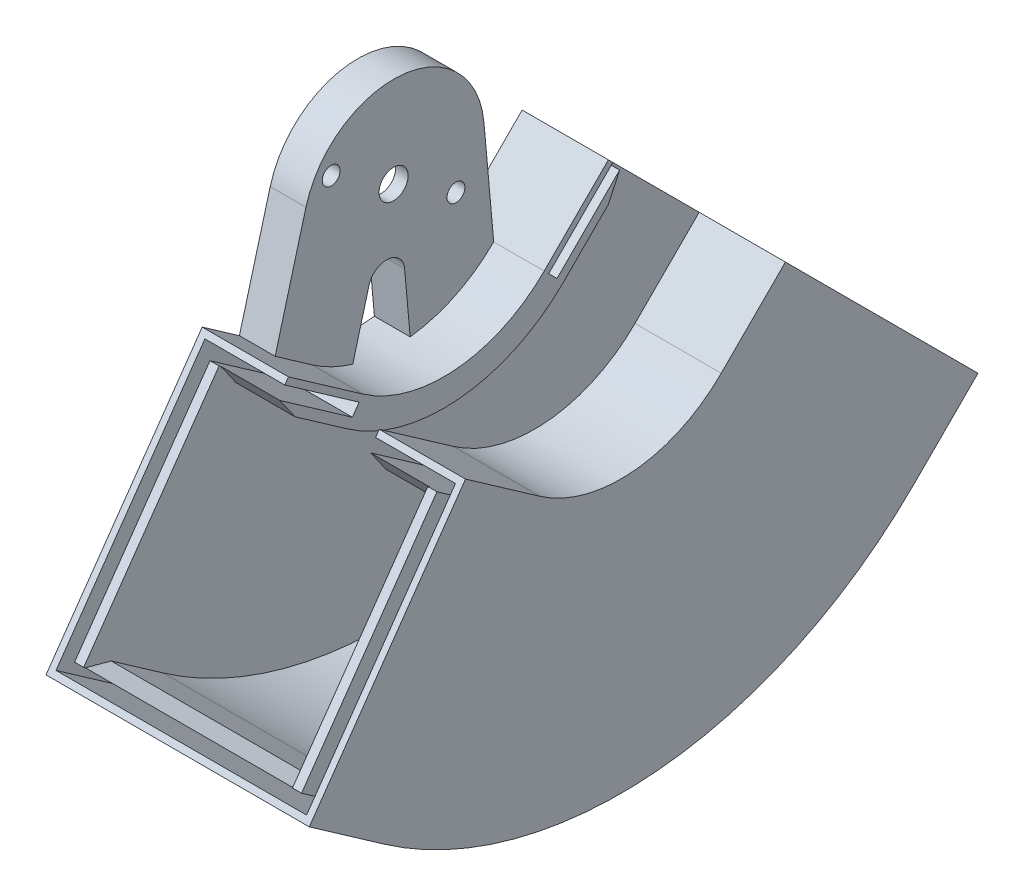
SolidWorks part; units mm, degrees
ref_plane "Front Plane" through (0, 0, 0) normal (0, 0, 1) x (1, 0, 0)
ref_plane "Top Plane" through (0, 0, 0) normal (0, 1, 0) x (1, 0, 0)
ref_plane "Right Plane" through (0, 0, 0) normal (1, 0, 0) x (0, 0, -1)
sketch "Sketch3" plane through (0, 0, 0) normal (1, 0, 0) x (0, 0, -1)
  line L0 (-22.7274, -32.4581) -> (-62.0633, -88.6355)
  line L1 (28.0184, -28.0184) -> (76.5118, -76.5118)
  line L2 (-22.7274, -32.4581) -> (0, 0) construction
  line L3 (0, 0) -> (28.0184, -28.0184) construction
  line L4 (0, 40.513) -> (0, -40.513) construction
  line L5 (-62.0633, -88.6355) -> (-66.4339, -94.8775)
  line L6 (76.5118, -76.5118) -> (81.8999, -81.8999)
  arc A2 (-62.0633, -88.6355) -> (76.5118, -76.5118) centre (0, 0) ccw
  arc A4 (-27.098, -38.7) -> (33.4066, -33.4066) centre (0, 0) ccw
  arc A5 (-22.7274, -32.4581) -> (28.0184, -28.0184) centre (0, 0) ccw
  arc A6 (-66.4339, -94.8775) -> (81.8999, -81.8999) centre (0, 0) ccw
  dimension "D1" = 216.408
  dimension "D2" = 135
  dimension "D3" = 94.488
  dimension "D4" = 7.62
  dimension "D6" = 7.62
  dimension "D5" = 80
extrude "Boss-Extrude2" add sketch "Sketch3" along normal blind 58.42 contours L5 A6 L6 A2 | A5 L0 A4 L1 region at (0, -39.9408, -3.4944) region at (0, -109.321, -9.5643)
sketch "Sketch4" plane through (58.42, 0, 0) normal (1, 0, 0) x (0, 0, -1)
  line L0 (-66.4339, -94.8775) -> (-22.7274, -32.4581)
  line L1 (28.0184, -28.0184) -> (81.8999, -81.8999)
  arc A0 (-22.7274, -32.4581) -> (28.0184, -28.0184) centre (0, 0) ccw
  arc A1 (-22.7274, -32.4581) -> (28.0184, -28.0184) centre (0, 0) ccw construction
  arc A2 (-66.4339, -94.8775) -> (81.8999, -81.8999) centre (0, 0) ccw
  arc A3 (-66.4339, -94.8775) -> (81.8999, -81.8999) centre (0, 0) ccw construction
  arc M1 (28.0184, -28.0184) -> (-22.7274, -32.4581) centre (0, 0) cw
  line M2 (-22.7274, -32.4581) -> (-27.098, -38.7)
  arc M3 (-27.098, -38.7) -> (33.4066, -33.4066) centre (0, 0) ccw
  line M4 (33.4066, -33.4066) -> (28.0184, -28.0184)
extrude "Boss-Extrude3" add sketch "Sketch4" along normal blind 7.62 contours L0 A2 L1 M3 | M4 M1 M2 M3 region at (58.42, -79.1939, -6.9286) region at (58.42, -39.9408, -3.4944)
ref_plane "Midplane" through (29.21, 0, 0) normal (-1, 0, 0) x (0, 0, 1)
mirror "Mirror1" about plane through (29.21, 0, 0) normal (-1, 0, 0) of "Boss-Extrude3"
sketch "Sketch6" plane through (0, 0, 0) normal (0, 0.5736, 0.8192) x (1, 0, 0)
  line L27 (-5.842, -41.402) -> (64.262, -41.402)
  line L28 (-5.842, -41.402) -> (-5.842, -114.046)
  line L29 (-5.842, -114.046) -> (64.262, -114.046)
  line L30 (64.262, -41.402) -> (64.262, -114.046)
  line L31 (-2.54, -44.704) -> (60.96, -44.704)
  line L32 (-2.54, -44.704) -> (-2.54, -110.744)
  line L33 (-2.54, -110.744) -> (60.96, -110.744)
  line L34 (60.96, -44.704) -> (60.96, -110.744)
  line L35 (58.42, -47.244) -> (0, -47.244) construction
  line L36 (0, -108.204) -> (0, -18.7894) construction
  line L37 (58.42, -18.7894) -> (58.42, -108.204) construction
  line L38 (58.42, -108.204) -> (0, -108.204) construction
  line L40 (0, -47.244) -> (58.42, -47.244)
  line L41 (0, -47.244) -> (0, -108.204)
  line L42 (0, -108.204) -> (58.42, -108.204)
  line L43 (58.42, -47.244) -> (58.42, -108.204)
  line L44 (-7.62, -39.624) -> (66.04, -39.624)
  line L45 (-7.62, -39.624) -> (-7.62, -115.824)
  line L46 (-7.62, -115.824) -> (66.04, -115.824)
  line L47 (66.04, -39.624) -> (66.04, -115.824)
  line M21 (-7.62, -39.624) -> (-7.62, -115.824)
  line M22 (-7.62, -115.824) -> (66.04, -115.824)
  line M23 (66.04, -115.824) -> (66.04, -39.624)
  line M24 (66.04, -39.624) -> (-7.62, -39.624)
  line M25 (58.42, -108.204) -> (0, -108.204)
  line M26 (0, -108.204) -> (0, -47.244)
  line M27 (0, -47.244) -> (58.42, -47.244)
  line M28 (58.42, -47.244) -> (58.42, -108.204)
  dimension "D1" = 3.302
  dimension "D2" = 3.302
  dimension "D3" = 3.302
  dimension "D4" = 3.302
  dimension "D5" = 2.54
  dimension "D6" = 2.54
  dimension "D7" = 2.54
  dimension "D8" = 2.54
extrude "Boss-Extrude4" add sketch "Sketch6" along normal blind 25.4 contours L27 L30 L29 L28 M24 M21 M22 M23 | L34 L31 L32 L33 M28 M25 M26 M27 region at (29.21, -37.3698, 26.1667) region at (29.21, -33.3262, 23.3353)
sketch "Sketch7" plane through (0, 0, 0) normal (0, 0.7071, -0.7071) x (1, 0, 0)
  line L0 (-5.842, 114.046) -> (64.262, 114.046)
  line L1 (-5.842, 114.046) -> (-5.842, 41.402)
  line L2 (-5.842, 41.402) -> (64.262, 41.402)
  line L3 (64.262, 114.046) -> (64.262, 41.402)
  line L4 (-2.54, 110.744) -> (60.96, 110.744)
  line L5 (-2.54, 110.744) -> (-2.54, 44.704)
  line L6 (-2.54, 44.704) -> (60.96, 44.704)
  line L7 (60.96, 110.744) -> (60.96, 44.704)
  line L8 (0, 108.204) -> (58.42, 108.204)
  line L9 (0, 108.204) -> (0, 47.244)
  line L10 (0, 47.244) -> (58.42, 47.244)
  line L11 (58.42, 108.204) -> (58.42, 47.244)
  line L12 (-7.62, 115.824) -> (66.04, 115.824)
  line L13 (-7.62, 115.824) -> (-7.62, 39.624)
  line L14 (-7.62, 39.624) -> (66.04, 39.624)
  line L15 (66.04, 115.824) -> (66.04, 39.624)
  line L16 (58.42, 108.204) -> (0, 108.204) construction
  line L17 (58.42, 47.244) -> (58.42, 108.204) construction
  line L18 (66.04, 115.824) -> (-7.62, 115.824) construction
  line L19 (66.04, 39.624) -> (66.04, 115.824) construction
  line L20 (-7.62, 39.624) -> (-7.62, 115.824) construction
  line L21 (66.04, 39.624) -> (-7.62, 39.624) construction
  line M17 (66.04, 115.824) -> (-7.62, 115.824)
  line M18 (-7.62, 115.824) -> (-7.62, 39.624)
  line M19 (-7.62, 39.624) -> (66.04, 39.624)
  line M20 (66.04, 39.624) -> (66.04, 115.824)
  line M21 (0, 47.244) -> (0, 108.204)
  line M22 (0, 108.204) -> (58.42, 108.204)
  line M23 (58.42, 108.204) -> (58.42, 47.244)
  line M24 (58.42, 47.244) -> (0, 47.244)
  dimension "D1" = 3.302
  dimension "D2" = 3.302
  dimension "D3" = 3.302
  dimension "D4" = 3.302
  dimension "D5" = 2.54
  dimension "D6" = 2.54
  dimension "D7" = 2.54
  dimension "D8" = 2.54
extrude "Boss-Extrude5" add sketch "Sketch7" along normal blind 25.4 contours L0 L3 L2 L1 M20 M17 M18 M19 | L7 L4 L5 L6 M24 M21 M22 M23 region at (29.21, -77.66, -77.66) region at (29.21, -81.1505, -81.1505)
chamfer "Chamfer1" distance 7.62 angle 20 4 edges at (29.21, -74.0667, 82.8697) (29.21, -24.1312, 47.9045) (29.21, -58.5513, -94.4723) (29.21, -15.446, -51.3671) first distance on face at (29.21, -81.3511, 72.4665) first distance on face at (29.21, -31.4156, 37.5013) first distance on face at (29.21, -67.5315, -85.492) first distance on face at (29.21, -24.4263, -42.3868)
ref_plane "Plane2" through (0, -13.9736, -1.2225) normal (0, -0.9962, -0.0872) x (-1, 0, 0)
sketch "Sketch10" plane through (0, -13.9736, -1.2225) normal (0, -0.9962, -0.0872) x (-1, 0, 0)
  line L0 (-66.04, 93.9078) -> (7.62, 93.9078) construction
  line L1 (-16.51, 95.5358) -> (-41.91, 95.5358)
  line L2 (-16.51, 95.5358) -> (-16.51, -82.1857)
  line L3 (-16.51, -82.1857) -> (-41.91, -82.1857)
  line L4 (-41.91, 95.5358) -> (-41.91, -82.1857)
  point P4 (-29.21, 93.9078)
  point P5 (-29.21, 95.5358)
  dimension "D1" = 25.4
extrude "Cut-Extrude3" cut sketch "Sketch10" along normal up to next
sketch "Sketch11" plane through (-7.62, 0, 0) normal (-1, 0, 0) x (0, 0, 1)
  line L0 (-25.2982, 2.2719) -> (-28.0184, -28.0184)
  line L4 (-3.0897, -22.02) -> (-4.6461, -39.3507)
  line L5 (6.8734, -21.1467) -> (11.421, -37.9424)
  line L6 (-17.454, -10.7521) -> (17.454, 10.7521) construction
  line L7 (24.5172, 6.6383) -> (33.1306, -25.1737)
  line L8 (43.5339, -17.8892) -> (22.7274, -32.4581) construction
  line L10 (1.5263, -17.4138) -> (-2.2178, 25.303) construction
  line L11 (22.7274, -32.4581) -> (43.5339, -17.8892)
  line L12 (22.7274, -32.4581) -> (33.1306, -25.1737)
  arc A1 (-28.0184, -28.0184) -> (22.7274, -32.4581) centre (0, 0) ccw construction
  circle A3 centre (0, 0) radius 4.064
  arc A4 (24.5172, 6.6383) -> (-25.2982, 2.2719) centre (0, 0) ccw
  circle A6 centre (-17.454, -10.7521) radius 2.5
  circle A7 centre (17.454, 10.7521) radius 2.5
  arc A8 (-3.0897, -22.02) -> (6.8734, -21.1467) centre (1.9699, -22.4744) cw
  arc A11 (11.421, -37.9424) -> (22.7274, -32.4581) centre (0, 0) ccw
  arc A12 (-28.0184, -28.0184) -> (22.7274, -32.4581) centre (0, 0) ccw
  arc A13 (-28.0184, -28.0184) -> (-4.6461, -39.3507) centre (0, 0) ccw
  point P22 (0, 0)
  dimension "D3" = 8.128
  dimension "D2" = 25.4
  dimension "D1" = 5
  dimension "D5" = 5.08
  dimension "D4" = 41
  dimension "D6" = 0
extrude "Boss-Extrude6" add sketch "Sketch11" against normal blind 10
sketch "Sketch12" plane through (-7.62, 0, 0) normal (-1, 0, 0) x (0, 0, 1)
  circle A0 centre (0, 0) radius 17
  dimension "D1" = 34
extrude "Cut-Extrude4" cut sketch "Sketch12" against normal blind 6.5
